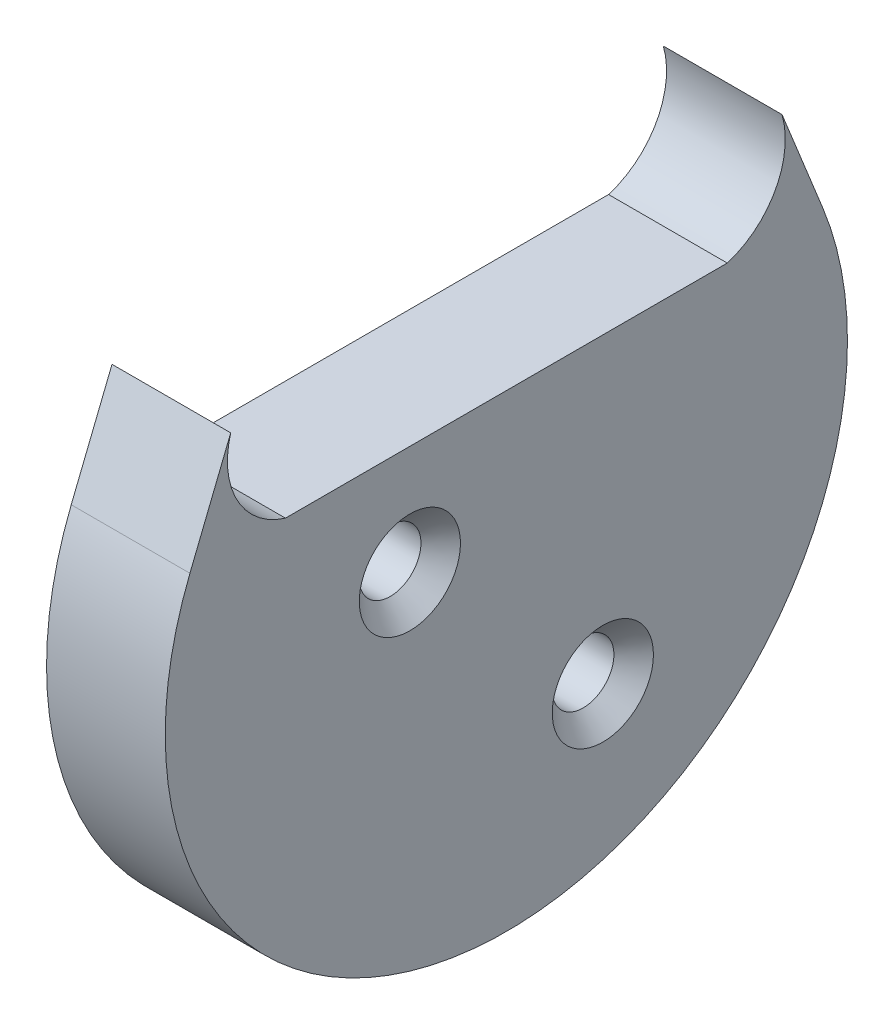
SolidWorks part; units mm, degrees
material "ABS"
ref_plane "Front" through (0, 0, 0) normal (0, 0, 1) x (1, 0, 0)
ref_plane "Top" through (0, 0, 0) normal (0, 1, 0) x (1, 0, 0)
ref_plane "Right" through (0, 0, 0) normal (1, 0, 0) x (0, 0, -1)
sketch "Sketch1" plane through (0, 0, 0) normal (1, 0, 0) x (0, 0, -1)
  line L0 (-11.5955, 4.6684) -> (11.5955, 4.6684)
  line L1 (-11.5955, 4.6684) -> (-10.1016, 8.379)
  line L2 (11.5955, 4.6684) -> (10.1016, 8.379)
  arc A0 (-11.5955, 4.6684) -> (11.5955, 4.6684) centre (0, 0) ccw
  arc A1 (-10.1016, 8.379) -> (-8.0955, 4.6684) centre (-7.2218, 7.5384) ccw
  arc A2 (10.1016, 8.379) -> (8.0955, 4.6684) centre (7.2218, 7.5384) cw
  dimension "D1" = 12.5
  dimension "D4" = 3.5
  dimension "3" = 3
  dimension "D2" = 23.191
  dimension "D3" = 4
  dimension "D5" = 3.5
extrude "Boss-Extrude1" add sketch "Sketch1" along normal mid plane 4.35 contours A1 L1 L0 | L2 A2 L0 | L0 A0 region at (0, 5.6196, 10.2621) region at (0, 5.6196, -10.2621)
sketch "Sketch2" plane through (2.175, 0, 0) normal (1, 0, 0) x (0, 0, -1)
  line L0 (0, 4.6684) -> (0, 0.6684) construction
  line L2 (-3.5355, 0.6684) -> (3.5355, 0.6684) construction
  line L3 (3.5355, 0.6684) -> (-3.5355, -6.4026) construction
  line L4 (-3.5355, 0.6684) -> (3.5355, -6.4026) construction
  line L5 (-8.0955, 4.6684) -> (8.0955, 4.6684) construction
  point P7 (0, 0.6684)
  point P10 (0, -2.8671)
  dimension "D1" = 4
  dimension "D2" = 10
hole_wizard "#2 Clearance Hole2" positions "3DSketch1" profile "Sketch6" hole size "#2" standard "ANSI Inch" end condition through all
sketch3d "3DSketch1"
  point P10 (2.175, 0.6684, 3.5355)
  point P13 (2.175, -6.4026, -3.5355)
sketch "Sketch6" plane through (2.175, 0.6684, 3.5355) normal (0, 1, 0) x (0, 0, -1)
  line L0 (0, 0) -> (0, 4.35)
  line L1 (0, 4.35) -> (1.1303, 4.35)
  line L2 (1.1303, 4.35) -> (1.1303, 0.7239)
  line L3 (1.1303, 0.7239) -> (1.8542, 0)
  line L5 (1.8542, 0) -> (0, 0)
  line L6 (-1.1303, 0.7239) -> (-1.8542, 0) construction
  line L11 (0, -6.35) -> (0, 107.95) construction
  dimension "Thru Hole Dia." = 2.2606
  dimension "Thru Hole Depth" = 4.35
  dimension "Near C'Sink Dia." = 3.7084
  dimension "Near C'Sink Angle" = 90
